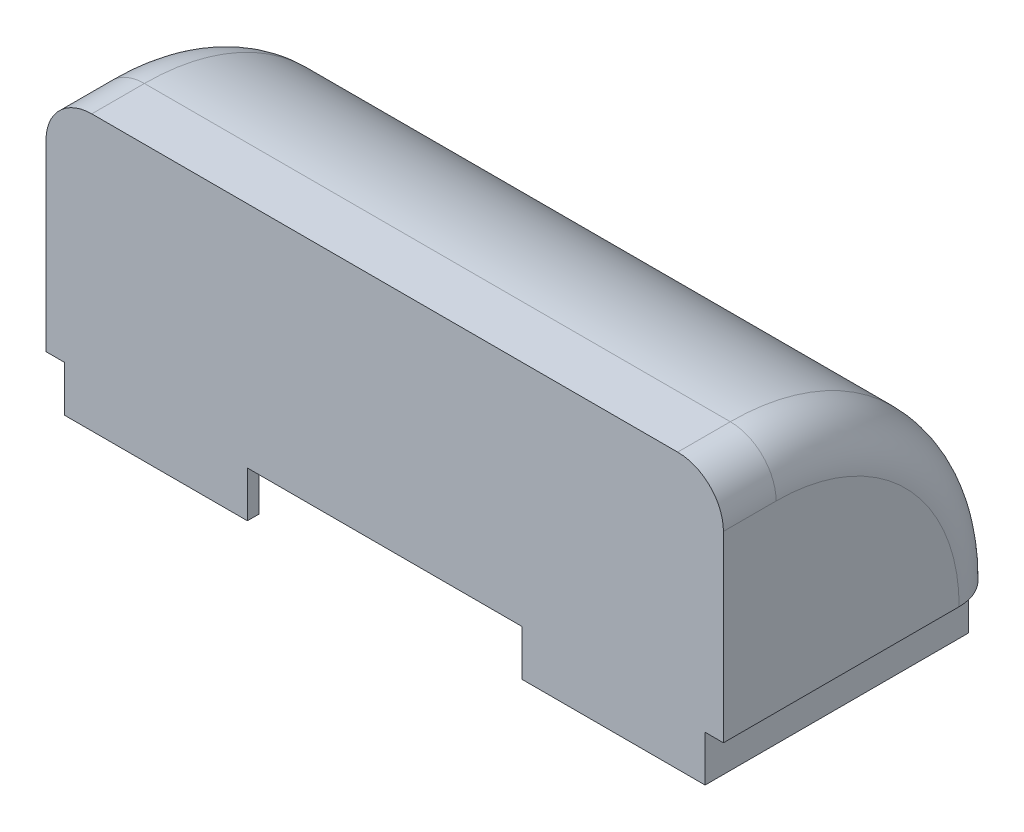
SolidWorks part; units mm, degrees
ref_plane "Front Plane" through (0, 0, 0) normal (0, 0, 1) x (1, 0, 0)
ref_plane "Top Plane" through (0, 0, 0) normal (0, 1, 0) x (1, 0, 0)
ref_plane "Right Plane" through (0, 0, 0) normal (1, 0, 0) x (0, 0, -1)
sketch "Sketch1" plane through (0, 0, 0) normal (0, 1, 0) x (1, 0, 0)
  line L0 (-13.5, 5.25) -> (-13.5, 5.75) construction
  line L1 (-14, 5.75) -> (14, 5.75)
  line L2 (-14, 5.75) -> (-14, -5.75)
  line L3 (-14, -5.75) -> (14, -5.75)
  line L4 (14, 5.75) -> (14, -5.75)
  line L5 (-14, 5.75) -> (14, -5.75) construction
  line L6 (-14, -5.75) -> (14, 5.75) construction
  line L7 (13.5, -5.25) -> (-13.5, -5.25)
  line L8 (13.5, -5.25) -> (13.5, 5.25)
  line L9 (13.5, 5.25) -> (-13.5, 5.25)
  line L10 (-13.5, -5.25) -> (-13.5, 5.25)
  line L11 (13.5, -5.25) -> (-13.5, 5.25) construction
  line L12 (13.5, 5.25) -> (-13.5, -5.25) construction
  line L13 (-13.5, 5.25) -> (-14, 5.25) construction
  line L14 (0, -5.75) -> (0, -5.25) construction
  line L16 (6, -5.75) -> (-6, -5.75)
  line L17 (6, -5.75) -> (6, -5.25)
  line L18 (6, -5.25) -> (-6, -5.25)
  line L19 (-6, -5.75) -> (-6, -5.25)
  line L20 (6, -5.75) -> (-6, -5.25) construction
  line L21 (6, -5.25) -> (-6, -5.75) construction
  point P0 (0, 0)
  point P6 (0, 0)
  point P15 (0, -5.5)
  dimension "D1" = 28
  dimension "D2" = 11.5
  dimension "D3" = 0.5
  dimension "D4" = 12
extrude "Boss-Extrude1" add sketch "Sketch1" along normal blind 2 contours L3 L19 L7 L10 L9 L8 L17 L4 L1 L2 region at (0, 0, -5.4473)
sketch "Sketch2" plane through (0, 2, 0) normal (0, 1, 0) x (1, 0, 0)
  line L12 (-5.2, -6.55) -> (5.2, -6.55)
  line L14 (-14.8, -5.75) -> (14.8, -5.75)
  line L24 (-14.8, -6.55) -> (-5.2, -6.55)
  line L25 (-5.2, -6.55) -> (-5.2, -4.45)
  line L26 (-5.2, -4.45) -> (-12.7, -4.45)
  line L27 (-12.7, -4.45) -> (-12.7, 4.45)
  line L28 (-12.7, 4.45) -> (12.7, 4.45)
  line L29 (12.7, 4.45) -> (12.7, -4.45)
  line L30 (12.7, -4.45) -> (5.2, -4.45)
  line L31 (5.2, -4.45) -> (5.2, -6.55)
  line L32 (5.2, -6.55) -> (14.8, -6.55)
  line L33 (14.8, -6.55) -> (14.8, 6.55)
  line L34 (14.8, 6.55) -> (-14.8, 6.55)
  line L35 (-14.8, 6.55) -> (-14.8, -6.55)
  line L36 (-14.8, -6.55) -> (-5.2, -6.55)
  line L37 (-5.2, -6.55) -> (-5.2, -4.45)
  line L38 (-5.2, -4.45) -> (-12.7, -4.45)
  line L39 (-12.7, -4.45) -> (-12.7, 4.45)
  line L40 (-12.7, 4.45) -> (12.7, 4.45)
  line L41 (12.7, 4.45) -> (12.7, -4.45)
  line L42 (12.7, -4.45) -> (5.2, -4.45)
  line L43 (5.2, -4.45) -> (5.2, -6.55)
  line L44 (5.2, -6.55) -> (14.8, -6.55)
  line L45 (14.8, -6.55) -> (14.8, 6.55)
  line L46 (14.8, 6.55) -> (-14.8, 6.55)
  line L47 (-14.8, 6.55) -> (-14.8, -6.55)
  line L49 (-14, -5.75) -> (-6, -5.75)
  line L50 (-6, -5.75) -> (-6, -5.25)
  line L51 (-6, -5.25) -> (-13.5, -5.25)
  line L52 (-13.5, -5.25) -> (-13.5, 5.25)
  line L53 (-13.5, 5.25) -> (13.5, 5.25)
  line L54 (13.5, 5.25) -> (13.5, -5.25)
  line L55 (13.5, -5.25) -> (6, -5.25)
  line L56 (6, -5.25) -> (6, -5.75)
  line L57 (6, -5.75) -> (14, -5.75)
  line L58 (14, -5.75) -> (14, 5.75)
  line L59 (14, 5.75) -> (-14, 5.75)
  line L60 (-14, 5.75) -> (-14, -5.75)
  line L61 (-14, -5.75) -> (-6, -5.75)
  line L62 (-6, -5.75) -> (-6, -5.25)
  line L63 (-6, -5.25) -> (-13.5, -5.25)
  line L64 (-13.5, -5.25) -> (-13.5, 5.25)
  line L65 (-13.5, 5.25) -> (13.5, 5.25)
  line L66 (13.5, 5.25) -> (13.5, -5.25)
  line L67 (13.5, -5.25) -> (6, -5.25)
  line L68 (6, -5.25) -> (6, -5.75)
  line L69 (6, -5.75) -> (14, -5.75)
  line L70 (14, -5.75) -> (14, 5.75)
  line L71 (14, 5.75) -> (-14, 5.75)
  line L72 (-14, 5.75) -> (-14, -5.75)
  line M25 (-14, -5.75) -> (-6, -5.75)
  line M26 (-6, -5.75) -> (-6, -5.25)
  line M27 (-6, -5.25) -> (-13.5, -5.25)
  line M28 (-13.5, -5.25) -> (-13.5, 5.25)
  line M29 (-13.5, 5.25) -> (13.5, 5.25)
  line M30 (13.5, 5.25) -> (13.5, -5.25)
  line M31 (13.5, -5.25) -> (6, -5.25)
  line M32 (6, -5.25) -> (6, -5.75)
  line M33 (6, -5.75) -> (14, -5.75)
  line M34 (14, -5.75) -> (14, 5.75)
  line M35 (14, 5.75) -> (-14, 5.75)
  line M36 (-14, 5.75) -> (-14, -5.75)
  dimension "D1" = 0.8
  dimension "D2" = 0
extrude "Boss-Extrude2" add sketch "Sketch2" along normal blind 10 contours L46 L47 L14 L45 M36 M35 M34 | M36 M25 M26 M27 M28 M29 M30 M31 M32 M33 M34 M35 | L42 L43 L14 L37 L38 L39 L40 L41 M32 M31 M30 M29 M28 M27 M26 | L43 L42 L41 L40 L39 L38 L37 L14 region at (0, 2, 0.2878) region at (-5.6, 2, 5.4585) region at (-14.4795, 2, -0.4) region at (-10, 2, 5.4473)
sketch "Sketch3" plane through (14.8, 0, 0) normal (1, 0, 0) x (0, 0, -1)
  line L0 (6.55, 2) -> (6.55, 12) construction
  line L1 (-5.75, 12) -> (6.55, 12) construction
  line L2 (6.55, 12) -> (-3.45, 12)
  line L3 (6.55, 12) -> (6.55, 2)
  arc A0 (6.55, 2) -> (-3.45, 12) centre (-3.45, 2) ccw
extrude "Cut-Extrude1" cut sketch "Sketch3" against normal up to next
fillet "Fillet1" radius 2 4 edges at (-14.8, 12, 4.6) (14.8, 12, 4.6) (-14.8, 9.0711, -3.6211) (14.8, 9.0711, -3.6211)
chamfer "Chamfer1" distance 2 angle 45 1 edges at (0, 2, -5.25)
